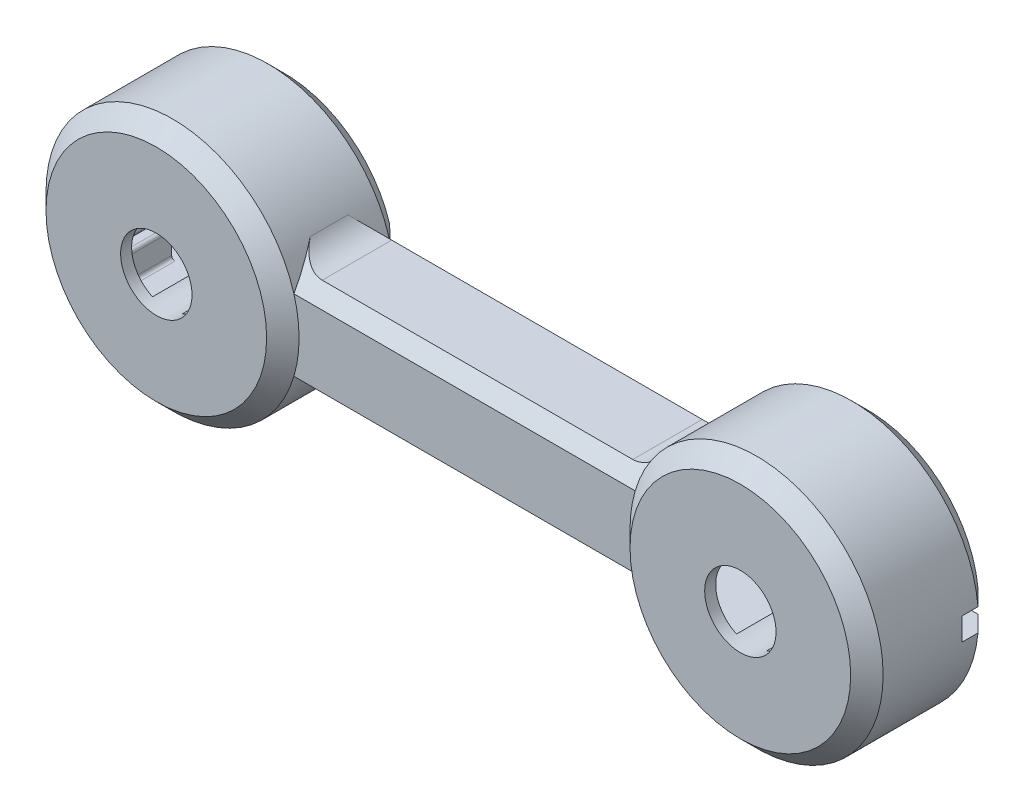
SolidWorks part; units mm, degrees
ref_plane "Front Plane" through (0, 0, 0) normal (0, 0, 1) x (1, 0, 0)
ref_plane "Top Plane" through (0, 0, 0) normal (0, 1, 0) x (1, 0, 0)
ref_plane "Right Plane" through (0, 0, 0) normal (1, 0, 0) x (0, 0, -1)
sketch "Sketch1" plane through (0, 0, 0) normal (0, 0, 1) x (1, 0, 0)
  line L0 (36, -15) -> (90, -15)
  line L1 (90, 15) -> (90, -15)
  line L2 (90, 15) -> (36, 15)
  line L3 (36, 15) -> (36, 0) construction
  line L4 (36, 0) -> (36, -15) construction
  line L5 (36, 0) -> (0, 0) construction
  arc A0 (36, 15) -> (36, -15) centre (0, 0) ccw
  circle A1 centre (0, 0) radius 11
  dimension "D1" = 22
  dimension "D2" = 28
  dimension "D3" = 90
  dimension "D4" = 30
extrude "Boss-Extrude1" add sketch "Sketch1" along normal blind 29.4
sketch "Sketch2" plane through (0, 0, 29.4) normal (0, 0, 1) x (1, 0, 0)
  arc A0 (36, 15) -> (36, -15) centre (0, 0) ccw construction
  circle A1 centre (0, 0) radius 11 construction
  arc A2 (36, 15) -> (36, -15) centre (0, 0) ccw
  circle A3 centre (0, 0) radius 11
  arc A4 (36, 15) -> (36, -15) centre (0, 0) cw
extrude "Boss-Extrude2" add sketch "Sketch2" along normal blind 5
sketch "Sketch4" plane through (0, 0, 0) normal (0, 0, -1) x (-1, 0, 0)
  line L0 (-43, 10) -> (-43, 15) construction
  line L1 (28, 10) -> (-43, 10)
  line L2 (28, 10) -> (28, -10)
  line L3 (28, -10) -> (-43, -10)
  line L4 (-43, 10) -> (-43, -10)
  line L5 (-90, 15) -> (-36, 15) construction
  line L6 (-43, -10) -> (-43, -15) construction
  line L7 (-36, -15) -> (-90, -15) construction
  line L8 (22, 10) -> (22, -10) construction
  line L24 (-43, 0) -> (39, 0) construction
  arc A1 (-36, -15) -> (-36, 15) centre (0, 0) ccw construction
  dimension "D1" = 22
  dimension "D2" = 20
  dimension "D3" = 43
  dimension "D4" = 6
extrude "Cut-Extrude1" cut sketch "Sketch4" against normal blind 18
sketch "Sketch5" plane through (0, 0, 18) normal (0, 0, -1) x (-1, 0, 0)
  line L0 (-43, 0) -> (28, 0) construction
  line L1 (-43, 10) -> (-43, -10) construction
  line L2 (28, -10) -> (28, 10) construction
  line L3 (-10.1, 0) -> (-10.1, 10) construction
  line L4 (-4.5826, 10) -> (-43, 10) construction
  circle A0 centre (-34.85, 5) radius 2.25
  circle A1 centre (14.65, 5) radius 2.25
  circle A2 centre (14.65, -5) radius 2.25
  circle A3 centre (-34.85, -5) radius 2.25
  point P18 (-10.1, 0)
  dimension "D3" = 4.5
  dimension "D1" = 10
  dimension "D2" = 49.5
  dimension "D4" = 14.65
extrude "Cut-Extrude2" cut sketch "Sketch5" against normal blind 5
ref_plane "Plane1" through (0, 0, 0) normal (0, 1, 0) x (1, 0, 0)
sketch "Sketch8" plane through (0, 0, 0) normal (0, 0, -1) x (-1, 0, 0)
  line L3 (-4.5826, -10) -> (-37.6962, -10)
  line L5 (-37.6962, 10) -> (-4.5826, 10)
  line L19 (4.5826, -10) -> (28, -10) construction
  line L20 (28, -10) -> (28, 10) construction
  line L21 (28, 10) -> (4.5826, 10) construction
  line L23 (4.5826, -10) -> (28, -10)
  line L24 (28, -10) -> (28, 10)
  line L25 (28, 10) -> (4.5826, 10)
  arc A6 (-4.5826, -10) -> (4.5826, -10) centre (0, 0) ccw construction
  arc A7 (4.5826, 10) -> (-4.5826, 10) centre (0, 0) ccw construction
  arc A8 (-4.5826, -10) -> (4.5826, -10) centre (0, 0) ccw
  arc A10 (4.5826, 10) -> (-4.5826, 10) centre (0, 0) ccw
  arc A24 (-36, -15) -> (-36, 15) centre (0, 0) ccw construction
  arc A25 (-36, -15) -> (-36, 15) centre (0, 0) ccw
  arc A26 (-36, 15) -> (-37.6962, 10) centre (0, 0) ccw
  arc A27 (-37.6962, -10) -> (-36, -15) centre (0, 0) ccw
extrude "Boss-Extrude3" add sketch "Sketch8" along normal blind 5
sketch "Sketch9" plane through (0, 0, -5) normal (0, 0, -1) x (-1, 0, 0)
  line L0 (28, 10) -> (28, -10) construction
  line L1 (28, 3.5) -> (38.8426, 3.5)
  line L3 (28, -3.5) -> (38.8426, -3.5)
  arc A2 (-36, 15) -> (-37.6962, 10) centre (0, 0) ccw construction
  arc A3 (38.8426, -3.5) -> (38.8426, 3.5) centre (0, 0) ccw
  dimension "D1" = 7
extrude "Cut-Extrude3" cut sketch "Sketch9" against normal blind 10 and the other way through all
sketch "Sketch7" plane through (0, 0, 0) normal (0, 1, 0) x (1, 0, 0)
  line L0 (-39, 0) -> (-34, 5)
  line L1 (-39, -5) -> (-39, -34.4) construction
  line L2 (37.6962, 5) -> (-38.8426, 5) construction
  line L3 (-34, 5) -> (-39, 5)
  line L4 (-39, 5) -> (-39, 0)
  line L5 (0, 0) -> (0, -34.4) construction
  line L6 (-39, -34.4) -> (39, -34.4) construction
  line L7 (-39, -29.4) -> (-34, -34.4)
  line L8 (-34, -34.4) -> (-39, -34.4)
  line L9 (-39, -34.4) -> (-39, -29.4)
  dimension "D1" = 5
revolve "Cut-Revolve1" cut sketch "Sketch7" angle 360 about L5
chamfer "Chamfer1" distance 4 angle 45 4 edges at (63, 15, 0) (63, -15, 0) (63, -15, 29.4) (63, 15, 29.4)
fillet "Fillet2" radius 10 2 edges at (36, -15, 14.7) (36, 15, 14.7)
sketch "Sketch10" plane through (0, 0, 18) normal (0, 0, -1) x (-1, 0, 0)
  line L1 (11.65, 10) -> (-32.35, 10)
  line L2 (11.65, 10) -> (11.65, 1.5)
  line L3 (11.65, -10) -> (-32.35, -10)
  line L5 (-43, -10) -> (-4.5826, -10) construction
  line L6 (-4.5826, 10) -> (-43, 10) construction
  line L12 (11.65, 1.5) -> (16.65, 1.5)
  line L14 (11.65, -1.5) -> (16.65, -1.5)
  line L15 (16.65, 1.5) -> (16.65, -1.5)
  line L16 (11.65, -1.5) -> (11.65, -10)
  line L17 (-10.35, 10) -> (-10.35, -10) construction
  line L18 (-32.35, -1.5) -> (-32.35, -10)
  line L19 (-32.35, -1.5) -> (-37.35, -1.5)
  line L20 (-37.35, 1.5) -> (-37.35, -1.5)
  line L21 (-32.35, 1.5) -> (-37.35, 1.5)
  line L22 (-32.35, 10) -> (-32.35, 1.5)
  circle A2 centre (14.65, 5) radius 2.25 construction
  dimension "D1" = 22
  dimension "D2" = 3
  dimension "D3" = 5
  dimension "D4" = 3
extrude "Cut-Extrude4" cut sketch "Sketch10" against normal blind 13
fillet "Fillet3" radius 1 16 edges at (32.35, -10, 24.5) (32.35, 10, 24.5) (37.35, 1.5, 24.5) (32.35, 1.5, 24.5) (37.35, -1.5, 24.5) (32.35, -1.5, 24.5) (-28, -10, 6.5) (-28, 10, 6.5) (43, -10, 9) (43, 10, 9) (-11.65, -10, 24.5) (-11.65, -1.5, 24.5) (-16.65, -1.5, 24.5) (-16.65, 1.5, 24.5) (-11.65, 1.5, 24.5) (-11.65, 10, 24.5)
sketch "Sketch11" plane through (0, 0, -5) normal (0, 0, -1) x (-1, 0, 0)
  line L0 (-27.5, 0) -> (27.5, 0) construction
  line L2 (11.77, 0) -> (-11.77, 0) construction
  arc A0 (27.5, 0) -> (-27.5, 0) centre (0, 0) ccw construction
  circle A1 centre (0, 27.5) radius 1.5
  circle A7 centre (23.8157, 13.75) radius 1.5
  circle A8 centre (23.8157, -13.75) radius 1.5
  circle A9 centre (0, -27.5) radius 1.5
  circle A10 centre (-23.8157, -13.75) radius 1.5
  circle A11 centre (-23.8157, 13.75) radius 1.5
  circle A12 centre (-52.5, 0) radius 1.5
  point P18 (0, 0)
  dimension "D1" = 55
  dimension "D2" = 3
  dimension "D3" = 6
  dimension "D4" = 52.5
extrude "Cut-Extrude5" cut sketch "Sketch11" against normal blind 10
mirror "Mirror4" about plane through (90, 15, 29.4) normal (-1, 0, 0) of bodies 110 105
